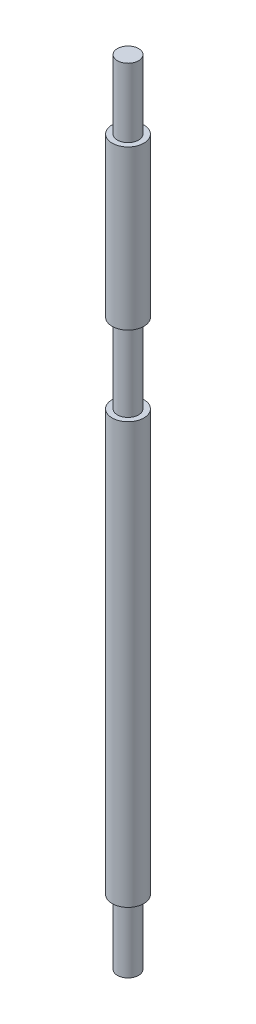
SolidWorks part; units mm, degrees
ref_plane "前视基准面" through (0, 0, 0) normal (0, 0, 1) x (1, 0, 0)
ref_plane "上视基准面" through (0, 0, 0) normal (0, 1, 0) x (1, 0, 0)
ref_plane "右视基准面" through (0, 0, 0) normal (1, 0, 0) x (0, 0, -1)
other "Configuration Table"
sketch "草图1" plane through (0, 0, 0) normal (0, 1, 0) x (1, 0, 0)
  circle A0 centre (0, 0) radius 1.5
  dimension "D1" = 3
extrude "凸台-拉伸1" add sketch "草图1" along normal mid plane 112.35
sketch "草图2" plane through (0, -56.175, 0) normal (0, -1, 0) x (1, 0, 0)
  circle A0 centre (0, 0) radius 2.25
  dimension "D1" = 4.5
extrude "凸台-拉伸2" add sketch "草图2" against normal up to surface (59.65 mm away) from offset 9.2 offset against normal yes
extrude "凸台-拉伸4" add sketch "草图2<4>" along normal blind 22.5 from offset 102.6 offset against normal yes
sketch "草图2<4>" plane through (0, -56.175, 0) normal (0, -1, 0) x (1, 0, 0) same geometry as "草图2"
